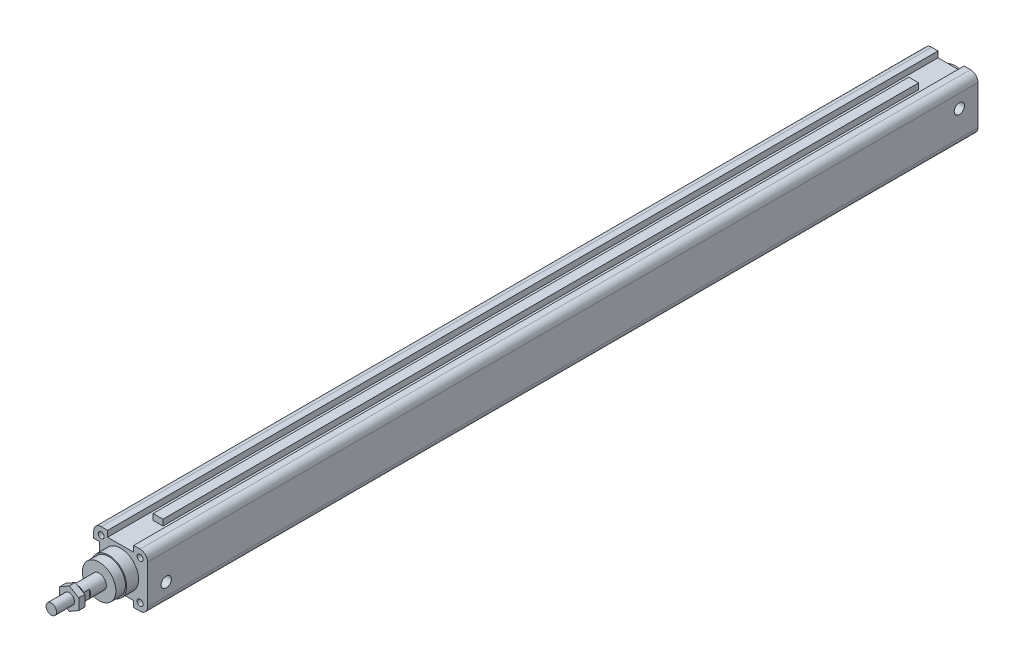
SolidWorks part; units mm, degrees
ref_plane "Front/Back" through (0, 0, 0) normal (0, 0, 1) x (1, 0, 0)
ref_plane "Top/Bottom" through (0, 0, 0) normal (0, 1, 0) x (1, 0, 0)
ref_plane "Right/Left" through (0, 0, 0) normal (1, 0, 0) x (0, 0, -1)
sketch "sk Body" plane through (0, 0, 0) normal (0, 0, 1) x (1, 0, 0)
  line L0 (0, 0) -> (0, 22.5) construction
  line L1 (-16.25, 22.5) -> (16.25, 22.5)
  line L2 (-22.5, 16.25) -> (-22.5, -16.25)
  line L3 (-16.25, -22.5) -> (16.25, -22.5)
  line L4 (22.5, 16.25) -> (22.5, -16.25)
  line L5 (0, 0) -> (22.5, 0) construction
  arc A0 (16.25, 22.5) -> (22.5, 16.25) centre (16.25, 16.25) cw
  arc A1 (16.25, -22.5) -> (22.5, -16.25) centre (16.25, -16.25) ccw
  arc A2 (-22.5, -16.25) -> (-16.25, -22.5) centre (-16.25, -16.25) ccw
  arc A3 (-16.25, 22.5) -> (-22.5, 16.25) centre (-16.25, 16.25) ccw
  point P9 (22.5, 22.5)
  point P12 (22.5, -22.5)
  dimension "E" = 45
  dimension "TG" = 32.5
extrude "Body" add sketch "sk Body" along normal mid plane 694
sketch "sk Front Taps" plane through (0, 0, 347) normal (0, 0, 1) x (1, 0, 0)
  circle A0 centre (16.25, 16.25) radius 2.5
  circle A1 centre (-16.25, 16.25) radius 2.5
  circle A2 centre (-16.25, -16.25) radius 2.5
  circle A3 centre (16.25, -16.25) radius 2.5
  dimension "RT" = 5
extrude "Front Taps" cut sketch "sk Front Taps" against normal blind 16
mirror "Back Taps" about plane through (0, 0, 0) normal (0, 0, 1) of "Front Taps"
sketch "sk Ports" plane through (22.5, 0, 0) normal (1, 0, 0) x (0, 0, -1)
  line L0 (-347, -16.25) -> (-347, 16.25) construction
  line L1 (347, -16.25) -> (347, 16.25) construction
  line L2 (0, 0) -> (-232.2227, 0) construction
  circle A0 centre (-331.4, -6) radius 4.283
  circle A1 centre (331.4, 5.2) radius 4.283
  dimension "EE" = 8.566
  dimension "J3" = 5.2
  dimension "J2" = 6
extrude "Ports" cut sketch "sk Ports" against normal blind 10
ref_plane "Front Cut Plane" through (0, 0, 315.8) normal (0, 0, 1) x (1, 0, 0)
ref_plane "Back Cut Plane" through (0, 0, -315.8) normal (0, 0, -1) x (-1, 0, 0)
sketch "sk Back Plate" plane through (0, 0, -347) normal (0, 0, -1) x (-1, 0, 0)
  circle A0 centre (0, 0) radius 15
  dimension "B" = 30
extrude "Back Plate" add sketch "sk Back Plate" along normal blind 4
ref_plane "Front Plane" through (0, 0, 347) normal (0, 0, -1) x (-1, 0, 0)
sketch "sk Front Plate" plane through (0, 0, 347) normal (0, 0, -1) x (-1, 0, 0)
  circle A0 centre (0, 0) radius 15
  dimension "B" = 30
extrude "Front Plate" add sketch "sk Front Plate" against normal blind 10
sketch "sk Rod Holder" plane through (0, 0, 347) normal (0, 0, -1) x (-1, 0, 0)
  circle A0 centre (0, 0) radius 14
  circle A1 centre (0, 0) radius 15 construction
  dimension "Offset" = 1
extrude "Rod Holder" add sketch "sk Rod Holder" against normal blind 18
sketch "sk Rod" plane through (0, 0, -347) normal (0, 0, -1) x (-1, 0, 0)
  circle A0 centre (0, 0) radius 6
  dimension "MM" = 12
extrude "Rod" add sketch "sk Rod" against normal blind 730
sketch "sk Rod Thread" plane through (0, 0, 383) normal (0, 0, 1) x (1, 0, 0)
  circle A0 centre (0, 0) radius 4.4
  dimension "KK" = 8.8
extrude "Rod Thread" add sketch "sk Rod Thread" along normal blind 22
sketch "sk Rod Flats" plane through (0, 0, 383) normal (0, 0, 1) x (1, 0, 0)
  line L0 (0, 0) -> (0, 9.8578) construction
  line L6 (-5, 3.3166) -> (-5, -3.3166)
  line L8 (5, 3.3166) -> (5, -3.3166)
  circle A0 centre (0, 0) radius 6 construction
  arc A2 (-5, 3.3166) -> (-5, -3.3166) centre (0, 0) ccw
  arc A3 (5, -3.3166) -> (5, 3.3166) centre (0, 0) ccw
  dimension "C1" = 10
extrude "Rod Flats" cut sketch "sk Rod Flats" against normal blind 5
sketch "sk Square Cut" plane through (0, 0, 383) normal (0, 0, 1) x (1, 0, 0)
  line L0 (0, 0) -> (0, 5) construction
  line L1 (-5, 5) -> (5, 5)
  line L2 (-5, 5) -> (-5, -5)
  line L3 (-5, -5) -> (5, -5)
  line L4 (5, 5) -> (5, -5)
  line L5 (0, 0) -> (5, 0) construction
  line L7 (-6, 6) -> (6, 6)
  line L8 (-6, 6) -> (-6, -6)
  line L9 (-6, -6) -> (6, -6)
  line L10 (6, 6) -> (6, -6)
  circle A0 centre (0, 0) radius 6 construction
  dimension "Square Rod" = 10
sketch "sk Sensor Slot" plane through (0, 0, 315.8) normal (0, 0, 1) x (1, 0, 0)
  line L0 (16.25, 22.5) -> (-16.25, 22.5) construction
  line L1 (-10.9, 22.5) -> (-4.1, 22.5)
  line L2 (-10.9, 22.5) -> (-10.9, 17.5)
  line L3 (-10.9, 17.5) -> (-4.1, 17.5)
  line L4 (-4.1, 22.5) -> (-4.1, 17.5)
  line L5 (7.5, 22.5) -> (-7.5, 22.5) construction
  line L6 (10.9, 22.5) -> (4.1, 22.5)
  line L7 (10.9, 22.5) -> (10.9, 17.5)
  line L8 (10.9, 17.5) -> (4.1, 17.5)
  line L9 (4.1, 22.5) -> (4.1, 17.5)
  line L10 (4.1, -22.5) -> (4.1, -17.5)
  line L11 (10.9, -17.5) -> (4.1, -17.5)
  line L13 (10.9, -22.5) -> (10.9, -17.5)
  line L14 (10.9, -22.5) -> (4.1, -22.5)
  line L15 (-10.9, -22.5) -> (-4.1, -22.5)
  line L16 (-10.9, -22.5) -> (-10.9, -17.5)
  line L17 (-10.9, -17.5) -> (-4.1, -17.5)
  line L18 (-4.1, -22.5) -> (-4.1, -17.5)
  line L20 (-7.5, 22.5) -> (-22.5, 22.5) construction
  line L21 (-22.5, 22.5) -> (-22.5, 7.5) construction
  line L22 (0, 0) -> (0, 22.5) construction
  line L23 (-22.5, -10.9) -> (-17.5, -10.9)
  line L24 (-22.5, -10.9) -> (-22.5, -4.1)
  line L25 (-22.5, -4.1) -> (-17.5, -4.1)
  line L26 (-17.5, -10.9) -> (-17.5, -4.1)
  line L27 (0, 0) -> (22.5, 0) construction
  line L28 (22.5, -16.25) -> (22.5, 16.25) construction
  line L29 (-16.25, 22.5) -> (16.25, 22.5) construction
  line L30 (-22.5, 7.5) -> (-22.5, -7.5) construction
  line L47 (-17.5, 10.9) -> (-17.5, 4.1)
  line L48 (-22.5, 4.1) -> (-17.5, 4.1)
  line L50 (-22.5, 10.9) -> (-22.5, 4.1)
  line L51 (-22.5, 10.9) -> (-17.5, 10.9)
  dimension "D1" = 6.8
  dimension "D2" = 5
extrude "Sensor Slot" cut sketch "sk Sensor Slot" against normal up to surface (631.6 mm away) up to plane "Back Cut Plane"
sketch "sk Front Cut" plane through (0, 0, 315.8) normal (0, 0, 1) x (1, 0, 0)
  line L0 (-10.9, 17.5) -> (10.9, 17.5)
  line L1 (10.9, 17.5) -> (10.9, 22.5)
  line L2 (10.9, 22.5) -> (-10.9, 22.5)
  line L3 (-10.9, 22.5) -> (-10.9, 17.5)
  line L4 (-17.5, 10.9) -> (-22.5, 10.9)
  line L5 (-22.5, 10.9) -> (-22.5, -10.9)
  line L6 (-22.5, -10.9) -> (-17.5, -10.9)
  line L7 (-17.5, -10.9) -> (-17.5, 10.9)
  line L8 (-10.9, -17.5) -> (10.9, -17.5)
  line L9 (10.9, -17.5) -> (10.9, -22.5)
  line L10 (10.9, -22.5) -> (-10.9, -22.5)
  line L11 (-10.9, -22.5) -> (-10.9, -17.5)
  line L12 (10.9, 22.5) -> (10.9, 17.5) construction
  line L13 (-22.5, 10.9) -> (-17.5, 10.9) construction
  line L15 (-10.9, 22.5) -> (-10.9, 17.5) construction
  line L16 (-10.9, 22.5) -> (-4.1, 22.5) construction
  line L18 (-10.9, 17.5) -> (-4.1, 17.5) construction
  line L19 (-17.5, 10.9) -> (-17.5, 4.1) construction
  line L20 (-22.5, 10.9) -> (-22.5, 4.1) construction
  line L29 (-10.9, -22.5) -> (-10.9, -17.5) construction
  line L30 (-10.9, -17.5) -> (-4.1, -17.5) construction
  line L31 (10.9, -22.5) -> (10.9, -17.5) construction
  line L32 (-10.9, -22.5) -> (-4.1, -22.5) construction
extrude "Front Cut" cut sketch "sk Front Cut" along normal up to next
sketch "sk Back Cut" plane through (0, 0, -315.8) normal (0, 0, -1) x (-1, 0, 0)
  line L0 (-10.9, 17.5) -> (-10.9, 22.5) construction
  line L1 (-10.9, 22.5) -> (10.9, 22.5) construction
  line L2 (10.9, 22.5) -> (10.9, 17.5) construction
  line L3 (22.5, -10.9) -> (17.5, -10.9) construction
  line L4 (17.5, -10.9) -> (17.5, 10.9) construction
  line L5 (17.5, 10.9) -> (22.5, 10.9) construction
  line L6 (22.5, 10.9) -> (22.5, -10.9) construction
  line L7 (10.9, -22.5) -> (10.9, -17.5) construction
  line L8 (-10.9, -22.5) -> (10.9, -22.5) construction
  line L9 (-10.9, -17.5) -> (-10.9, -22.5) construction
  line L10 (10.9, -17.5) -> (-10.9, -17.5) construction
  line L11 (10.9, 17.5) -> (-10.9, 17.5) construction
  line L12 (-10.9, 17.5) -> (-10.9, 22.5)
  line L13 (-10.9, 22.5) -> (10.9, 22.5)
  line L14 (10.9, 22.5) -> (10.9, 17.5)
  line L15 (22.5, -10.9) -> (17.5, -10.9)
  line L16 (17.5, -10.9) -> (17.5, 10.9)
  line L17 (17.5, 10.9) -> (22.5, 10.9)
  line L18 (22.5, 10.9) -> (22.5, -10.9)
  line L19 (10.9, -22.5) -> (10.9, -17.5)
  line L20 (-10.9, -22.5) -> (10.9, -22.5)
  line L21 (-10.9, -17.5) -> (-10.9, -22.5)
  line L22 (10.9, -17.5) -> (-10.9, -17.5)
  line L23 (10.9, 17.5) -> (-10.9, 17.5)
extrude "Back Cut" cut sketch "sk Back Cut" along normal up to next
ref_plane "Nut Plane" through (0, 0, 385) normal (0, 0, 1) x (1, 0, 0)
sketch "sk Rod Nut" plane through (0, 0, 385) normal (0, 0, 1) x (1, 0, 0)
  line L1 (0, -9.2376) -> (8, -4.6188)
  line L2 (8, -4.6188) -> (8, 4.6188)
  line L3 (8, 4.6188) -> (0, 9.2376)
  line L4 (0, 9.2376) -> (-8, 4.6188)
  line L5 (-8, 4.6188) -> (-8, -4.6188)
  line L6 (-8, -4.6188) -> (0, -9.2376)
  circle A0 centre (0, 0) radius 8 construction
  dimension "C2" = 16
extrude "Rod Nut" add sketch "sk Rod Nut" along normal blind 5
extrude "Square Cut" [suppressed] cut sketch "sk Square Cut" against normal up to surface (8.5 mm away)
sketch "sk Square Rod" [suppressed] plane through (0, 0, 137.5) normal (0, 0, 1) x (1, 0, 0)
  line L0 (8, 8) -> (8, -8) construction
  line L1 (-8, -8) -> (8, -8) construction
  line L2 (-8, 8) -> (-8, -8) construction
  line L3 (-8, 8) -> (8, 8) construction
  line L4 (8, 8) -> (8, -8)
  line L5 (-8, -8) -> (8, -8)
  line L6 (-8, 8) -> (-8, -8)
  line L7 (-8, 8) -> (8, 8)
extrude "Square Rod" [suppressed] add sketch "sk Square Rod" against normal blind 730
sketch "sk K2" [suppressed] plane through (0, 0, 162) normal (0, 0, 1) x (1, 0, 0)
  circle A0 centre (0, 0) radius 7.25 construction
  circle A1 centre (0, 0) radius 7.25
extrude "K2" [suppressed] add sketch "sk K2" along normal blind 70
sketch "sk K3" plane through (0, 0, 383) normal (0, 0, 1) x (1, 0, 0)
  circle A0 centre (0, 0) radius 2.5
  dimension "KF" = 5
extrude "K3" [suppressed] cut sketch "sk K3" against normal blind 12
ref_plane "Mirror Plane" [suppressed] through (0, 0, 0) normal (0, 0, -1) x (-1, 0, 0)
mirror "Double Rod Holder" [suppressed] about plane through (0, 0, 0) normal (0, 0, -1)
sketch "sk Double Rod" plane through (0, 0, -347) normal (0, 0, -1) x (-1, 0, 0)
  circle A0 centre (0, 0) radius 6 construction
  circle A1 centre (0, 0) radius 6
extrude "Double Rod" [suppressed] add sketch "sk Double Rod" along normal offset from surface (121 mm away) 1348
sketch "sk Double Thread" [suppressed] plane through (0, 0, -221.5) normal (0, 0, -1) x (-1, 0, 0)
  circle A0 centre (0, 0) radius 7.25 construction
  circle A1 centre (0, 0) radius 7.25
extrude "Double Thread" [suppressed] add sketch "sk Double Thread" along normal blind 22
sketch "sk Double Rod Flats" [suppressed] plane through (0, 0, -221.5) normal (0, 0, -1) x (-1, 0, 0)
  line L0 (-8.5, 5.2678) -> (-8.5, -5.2678) construction
  line L1 (8.5, 5.2678) -> (8.5, -5.2678) construction
  line L2 (-8.5, 5.2678) -> (-8.5, -5.2678)
  line L3 (8.5, 5.2678) -> (8.5, -5.2678)
  arc A0 (-8.5, 5.2678) -> (-8.5, -5.2678) centre (0, 0) ccw construction
  arc A1 (8.5, -5.2678) -> (8.5, 5.2678) centre (0, 0) ccw construction
  arc A2 (-8.5, 5.2678) -> (-8.5, -5.2678) centre (0, 0) ccw
  arc A3 (8.5, -5.2678) -> (8.5, 5.2678) centre (0, 0) ccw
extrude "Double Rod Flats" [suppressed] cut sketch "sk Double Rod Flats" against normal blind 5
ref_plane "Double Nut Plane" [suppressed] through (0, 0, -238.5) normal (0, 0, -1) x (-1, 0, 0)
sketch "sk Double Rod Nut" [suppressed] plane through (0, 0, -238.5) normal (0, 0, -1) x (-1, 0, 0)
  line L0 (-12, 6.9282) -> (0, 13.8564) construction
  line L1 (0, 13.8564) -> (12, 6.9282) construction
  line L2 (12, 6.9282) -> (12, -6.9282) construction
  line L3 (12, -6.9282) -> (0, -13.8564) construction
  line L4 (0, -13.8564) -> (-12, -6.9282) construction
  line L5 (-12, -6.9282) -> (-12, 6.9282) construction
  line L6 (-12, 6.9282) -> (0, 13.8564)
  line L7 (0, 13.8564) -> (12, 6.9282)
  line L8 (12, 6.9282) -> (12, -6.9282)
  line L9 (12, -6.9282) -> (0, -13.8564)
  line L10 (0, -13.8564) -> (-12, -6.9282)
  line L11 (-12, -6.9282) -> (-12, 6.9282)
extrude "Double Rod Nut" [suppressed] add sketch "sk Double Rod Nut" along normal blind 5
sketch "Sketch2" [suppressed] plane through (0, 0, -171) normal (0, 0, -1) x (-1, 0, 0)
  circle A0 centre (0, 0) radius 7.25 construction
  circle A1 centre (0, 0) radius 7.25
extrude "Double K2" [suppressed] add sketch "Sketch2" along normal blind 70
sketch "sk Double K3" [suppressed] plane through (0, 0, -221.5) normal (0, 0, -1) x (-1, 0, 0)
  circle A0 centre (0, 0) radius 4.25 construction
  circle A1 centre (0, 0) radius 4.25
extrude "Double K3" [suppressed] cut sketch "sk Double K3" against normal blind 12
sketch "sk S20" [suppressed] plane through (0, 0, 169.5) normal (0, 0, 1) x (1, 0, 0)
  circle A0 centre (0, 0) radius 4
  dimension "D8" = 4.5
extrude "S20" [suppressed] cut sketch "sk S20" against normal through all
sketch "sk KP Ext" plane through (0, 0, 347) normal (0, 0, 1) x (1, 0, 0)
  line L0 (10.9, -22.5) -> (16.25, -22.5) construction
  line L1 (22.5, -16.25) -> (22.5, 16.25) construction
  line L2 (10.9, 22.5) -> (10.9, 17.5) construction
  line L3 (16.25, 22.5) -> (10.9, 22.5) construction
  line L4 (10.9, -17.5) -> (10.9, -22.5) construction
  line L5 (-10.9, -17.5) -> (10.9, -17.5) construction
  line L6 (-10.9, -22.5) -> (-10.9, -17.5) construction
  line L7 (-16.25, -22.5) -> (-10.9, -22.5) construction
  line L8 (-22.5, -10.9) -> (-22.5, -16.25) construction
  line L9 (-17.5, -10.9) -> (-22.5, -10.9) construction
  line L10 (-17.5, 10.9) -> (-17.5, -10.9) construction
  line L11 (-22.5, 10.9) -> (-17.5, 10.9) construction
  line L12 (-22.5, 16.25) -> (-22.5, 10.9) construction
  line L13 (-10.9, 22.5) -> (-16.25, 22.5) construction
  line L14 (10.9, 17.5) -> (-10.9, 17.5) construction
  line L15 (-10.9, 17.5) -> (-10.9, 22.5) construction
  line L16 (10.9, -22.5) -> (16.25, -22.5)
  line L17 (22.5, -16.25) -> (22.5, 16.25)
  line L18 (10.9, 22.5) -> (10.9, 17.5)
  line L19 (16.25, 22.5) -> (10.9, 22.5)
  line L20 (10.9, -17.5) -> (10.9, -22.5)
  line L21 (-10.9, -17.5) -> (10.9, -17.5)
  line L22 (-10.9, -22.5) -> (-10.9, -17.5)
  line L23 (-16.25, -22.5) -> (-10.9, -22.5)
  line L24 (-22.5, -10.9) -> (-22.5, -16.25)
  line L25 (-17.5, -10.9) -> (-22.5, -10.9)
  line L26 (-17.5, 10.9) -> (-17.5, -10.9)
  line L27 (-22.5, 10.9) -> (-17.5, 10.9)
  line L28 (-22.5, 16.25) -> (-22.5, 10.9)
  line L29 (-10.9, 22.5) -> (-16.25, 22.5)
  line L30 (10.9, 17.5) -> (-10.9, 17.5)
  line L31 (-10.9, 17.5) -> (-10.9, 22.5)
  arc A0 (16.25, -22.5) -> (22.5, -16.25) centre (16.25, -16.25) ccw construction
  arc A1 (22.5, 16.25) -> (16.25, 22.5) centre (16.25, 16.25) ccw construction
  circle A2 centre (-16.25, 16.25) radius 2.5 construction
  circle A3 centre (16.25, 16.25) radius 2.5 construction
  circle A4 centre (-16.25, -16.25) radius 2.5 construction
  circle A5 centre (16.25, -16.25) radius 2.5 construction
  arc A6 (-22.5, -16.25) -> (-16.25, -22.5) centre (-16.25, -16.25) ccw construction
  arc A7 (-16.25, 22.5) -> (-22.5, 16.25) centre (-16.25, 16.25) ccw construction
  arc A8 (16.25, -22.5) -> (22.5, -16.25) centre (16.25, -16.25) ccw
  arc A9 (22.5, 16.25) -> (16.25, 22.5) centre (16.25, 16.25) ccw
  circle A10 centre (-16.25, 16.25) radius 2.5
  circle A11 centre (16.25, 16.25) radius 2.5
  circle A12 centre (-16.25, -16.25) radius 2.5
  circle A13 centre (16.25, -16.25) radius 2.5
  arc A14 (-22.5, -16.25) -> (-16.25, -22.5) centre (-16.25, -16.25) ccw
  arc A15 (-16.25, 22.5) -> (-22.5, 16.25) centre (-16.25, 16.25) ccw
extrude "KP Ext" [suppressed] add sketch "sk KP Ext" along normal up to surface (53 mm away)
sketch "sk Clamp" [suppressed] plane through (27, 0, 0) normal (1, 0, 0) x (0, 0, -1)
  line L0 (0, 0) -> (-102, 0) construction
  line L1 (-118, 19) -> (-118, -19) construction
  circle A0 centre (-102, 0) radius 12
  dimension "D1" = 20
  dimension "L5" = 14
extrude "Clamp" [suppressed] add sketch "sk Clamp" along normal blind 22
sketch "sk Clamp Connect" [suppressed] plane through (61, 0, 0) normal (1, 0, 0) x (0, 0, -1)
  circle A0 centre (-102, 0) radius 4.283
  dimension "D2" = 4.2
extrude "Clamp Connect" [suppressed] cut sketch "sk Clamp Connect" against normal blind 22
